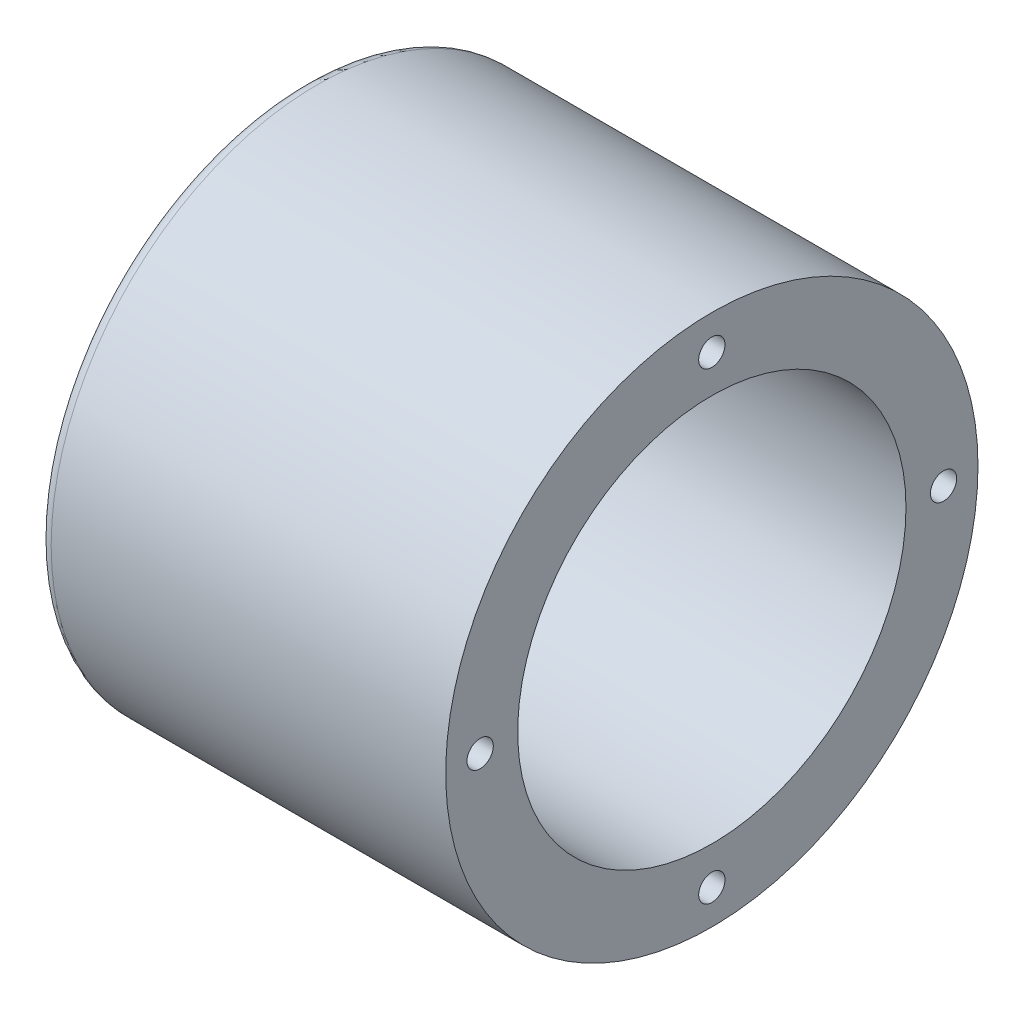
SolidWorks part; units mm, degrees
ref_plane "Front Plane" through (0, 0, 0) normal (0, 0, 1) x (1, 0, 0)
ref_plane "Top Plane" through (0, 0, 0) normal (0, 1, 0) x (1, 0, 0)
ref_plane "Right Plane" through (0, 0, 0) normal (1, 0, 0) x (0, 0, -1)
ref_axis "X-Axis" through (88.99, 0, 0) along (-1, 0, 0)
ref_axis "Y-Axis" through (0, 0, -88.99) along (0, 0, 1)
ref_axis "Z-Axis" through (0, -55, 0) along (0, 1, 0)
sketch "Sketch1" plane through (0, 0, 0) normal (0, 0, 1) x (1, 0, 0)
  line L0 (88.99, 0) -> (-88.99, 0) construction
  line L1 (-32.5, 42.5) -> (32.5, 42.5)
  line L2 (-32.5, 42.5) -> (-32.5, 28.5)
  line L3 (-28.5, 31) -> (32.5, 31)
  line L4 (32.5, 42.5) -> (32.5, 31)
  line L5 (0, -55) -> (0, 55) construction
  line L9 (-32.5, 28.5) -> (-28.5, 28.5)
  line L10 (-28.5, 31) -> (-28.5, 28.5)
  point P6 (0, 42.5)
  dimension "D1" = 31
  dimension "D2" = 42.5
  dimension "D3" = 65
  dimension "D4" = 2.5
  dimension "D5" = 4
revolve "Revolve1" add sketch "Sketch1" angle 360 about axis through (88.99, 0, 0) along (-1, 0, 0)
fillet "Fillet1" radius 2 1 edges at (-32.5, 0, -42.5)
chamfer "Chamfer1" distance 1 angle 45 1 edges at (-32.5, 0, -28.5)
sketch "Sketch3" plane through (32.5, 0, 0) normal (1, 0, 0) x (0, 0, -1)
  line L0 (0, -55) -> (0, 55) construction
  point P0 (0, 37)
  point P1 (0, 0)
  dimension "D1" = 37
hole_wizard "Tap Drill for M5x0.8 Tap1" positions "3DSketch1" profile "Sketch5" hole size "M5x0.8" standard "ANSI Metric"
sketch3d "3DSketch1"
  point P0 (32.5, 37, 0)
sketch "Sketch5" plane through (32.5, 37, 0) normal (0, 1, 0) x (0, 0, -1)
  line L0 (0, 0) -> (0, 21.2618)
  line L1 (0, 21.2618) -> (2.1, 20)
  line L2 (2.1, 20) -> (2.1, 0)
  line L5 (2.1, 0) -> (0, 0)
  line L10 (0, 21.2618) -> (-2.1, 20) construction
  line L11 (0, -6.35) -> (0, 107.95) construction
  dimension "Hole Dia." = 4.2
  dimension "Hole Depth" = 20
  dimension "Drill Angle" = 118
pattern_circular "CirPattern1" count 4 over 360 about axis through (88.99, 0, 0) along (-1, 0, 0) of "Tap Drill for M5x0.8 Tap1"
